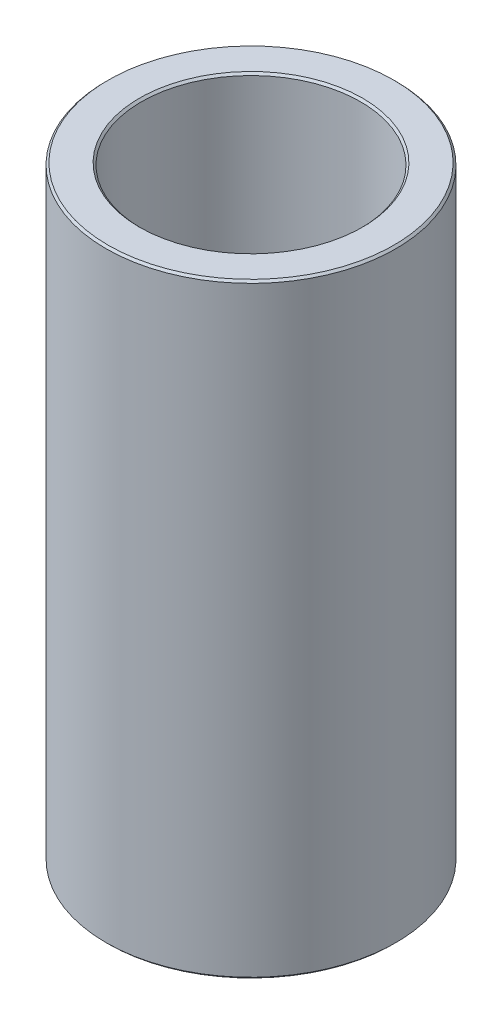
SolidWorks part; units mm, degrees
ref_plane "Front Plane" through (0, 0, 0) normal (0, 0, 1) x (1, 0, 0)
ref_plane "Top Plane" through (0, 0, 0) normal (0, 1, 0) x (1, 0, 0)
ref_plane "Right Plane" through (0, 0, 0) normal (1, 0, 0) x (0, 0, -1)
sketch "Sketch1" plane through (0, 0, 0) normal (0, 1, 0) x (1, 0, 0)
  circle A0 centre (0, 0) radius 52.5
  dimension "SLEEVE_OD" = 105
extrude "Boss-Extrude1" add sketch "Sketch1" along normal blind 219.1313
sketch "Sketch2" plane through (0, 0, 0) normal (0, 1, 0) x (1, 0, 0)
  circle A0 centre (0, 0) radius 39.7036
  dimension "BORE_D" = 79.4072
extrude "Cut-Extrude1" cut sketch "Sketch2" along normal through all
chamfer "Chamfer1" distance 0.7431 angle 45 4 edges at (0, 219.1313, 39.7036) (0, 0, 39.7036) (0, 0, 52.5) (0, 219.1313, 52.5)
